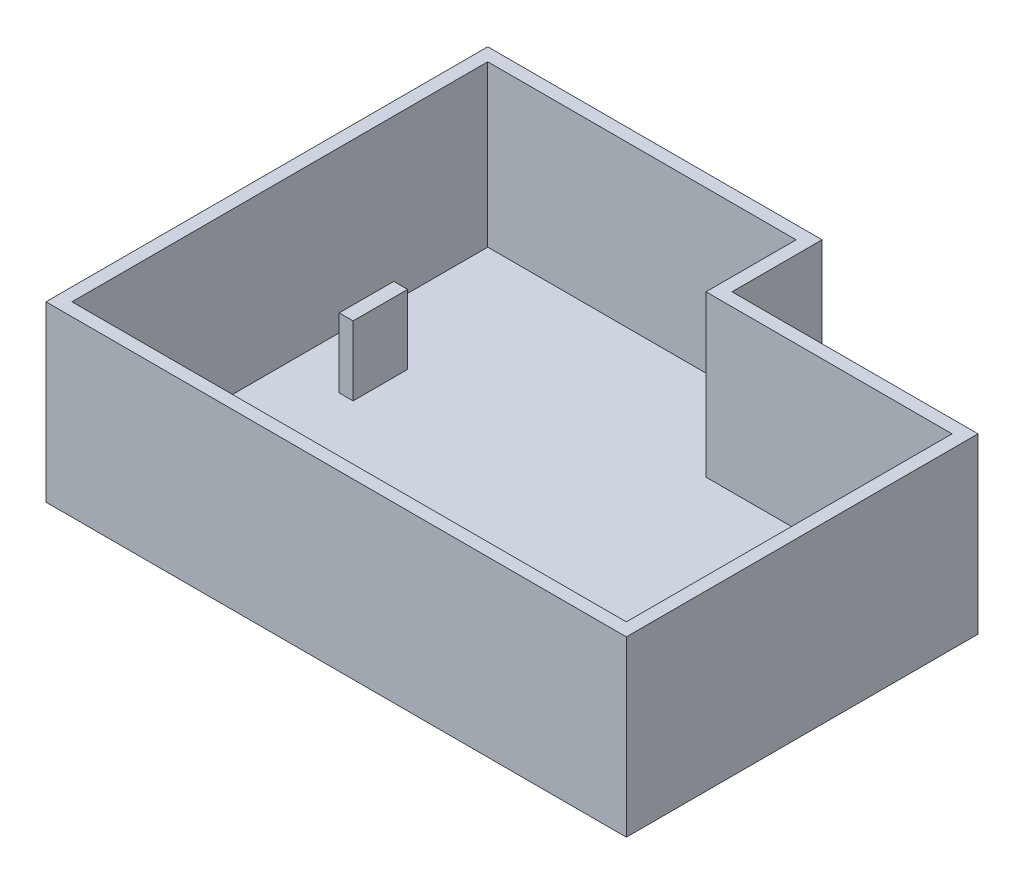
SolidWorks part; units mm, degrees
material "Cedro"
ref_plane "Alzado" through (0, 0, 0) normal (0, 0, 1) x (1, 0, 0)
ref_plane "Planta" through (0, 0, 0) normal (0, 1, 0) x (1, 0, 0)
ref_plane "Vista lateral" through (0, 0, 0) normal (1, 0, 0) x (0, 0, -1)
sketch "Croquis1" plane through (0, 0, 0) normal (0, 1, 0) x (1, 0, 0)
  line L0 (-106.3625, -93.6625) -> (-106.3625, 93.6625)
  line L1 (-101.6, -88.9) -> (101.6, -88.9)
  line L2 (-101.6, -88.9) -> (-101.6, 88.9)
  line L3 (-101.6, 88.9) -> (101.6, 88.9)
  line L4 (101.6, -88.9) -> (101.6, 88.9)
  line L5 (-101.6, -88.9) -> (101.6, 88.9) construction
  line L6 (-101.6, 88.9) -> (101.6, -88.9) construction
  line L7 (-106.3625, 93.6625) -> (106.3625, 93.6625)
  line L8 (106.3625, -93.6625) -> (106.3625, 93.6625)
  line L9 (-106.3625, -93.6625) -> (106.3625, -93.6625)
  point P0 (0, 0)
  dimension "D1" = 203.2
  dimension "D2" = 177.8
  dimension "D3" = 4.7625
extrude "Saliente-Extruir1" add sketch "Croquis1" along normal blind 63.608 contours L1 L4 L3 L2 | L0 L9 L8 L7 L4 L1 L2 L3 region at (-103.528, 0, 0) region at (0, 0, 0)
shell "Vaciado1" thickness 4.7625 removed face at (0, 63.608, 0)
sketch "Croquis2" plane through (0, 4.7625, 0) normal (0, 1, 0) x (1, 0, 0)
  line L0 (-77.47, 10) -> (-77.47, -10)
  line L1 (-101.6, 88.9) -> (101.6, 88.9) construction
  line L3 (10, -64.77) -> (-10, -64.77)
  line L4 (-54.45, 58.42) -> (-34.45, 58.42)
  line L5 (-101.6, -88.9) -> (-101.6, 88.9) construction
  line L6 (-101.6, -88.9) -> (101.6, -88.9) construction
  line L7 (101.6, -88.9) -> (101.6, 88.9) construction
  line L8 (-54.45, 58.42) -> (-54.45, 68.58)
  line L9 (-54.45, 63.5) -> (-34.45, 63.5)
  line L10 (-54.45, 68.58) -> (-34.45, 68.58)
  line L13 (-34.45, 58.42) -> (-34.45, 68.58)
  line L14 (77.47, -18.575) -> (77.47, -38.575)
  line L15 (-54.45, 58.42) -> (-34.45, 68.58) construction
  line L16 (-54.45, 68.58) -> (-34.45, 58.42) construction
  line L17 (72.39, -38.575) -> (82.55, -38.575)
  line L18 (72.39, -38.575) -> (72.39, -18.575)
  line L19 (72.39, -18.575) -> (82.55, -18.575)
  line L20 (82.55, -38.575) -> (82.55, -18.575)
  line L21 (72.39, -38.575) -> (82.55, -18.575) construction
  line L22 (72.39, -18.575) -> (82.55, -38.575) construction
  line L23 (-10, -69.85) -> (10, -69.85)
  line L24 (-10, -69.85) -> (-10, -59.69)
  line L25 (-10, -59.69) -> (10, -59.69)
  line L26 (10, -69.85) -> (10, -59.69)
  line L27 (-10, -69.85) -> (10, -59.69) construction
  line L28 (-10, -59.69) -> (10, -69.85) construction
  line L29 (-72.39, -10) -> (-82.55, -10)
  line L30 (-72.39, -10) -> (-72.39, 10)
  line L31 (-72.39, 10) -> (-82.55, 10)
  line L32 (-82.55, -10) -> (-82.55, 10)
  line L33 (-72.39, -10) -> (-82.55, 10) construction
  line L34 (-72.39, 10) -> (-82.55, -10) construction
  point P1 (-44.45, 63.5)
  point P17 (77.47, -28.575)
  point P23 (0, -64.77)
  point P29 (-77.47, 0)
  dimension "D1" = 24.13
  dimension "D2" = 24.13
  dimension "D3" = 24.13
  dimension "D4" = 25.4
  dimension "D7" = 20
  dimension "D8" = 10.16
extrude "Saliente-Extruir3" add sketch "Croquis2" along normal blind 25.4 contours L9 L13 L10 L8 | L32 L29 L0 L31 | L23 L26 L3 L24 | L17 L20 L19 L14 region at (-80.01, 4.7625, 0) region at (0, 4.7625, 67.31) region at (-44.45, 4.7625, -66.04) region at (80.01, 4.7625, 28.575)
extrude "Saliente-Extruir4" add sketch "Croquis2<5>" along normal blind 6.5 contours L30 L31 L0 L29 | L3 L26 L25 L24 | L19 L18 L17 L14 region at (-74.93, 4.7625, 0) region at (0, 4.7625, 62.23) region at (74.93, 4.7625, 28.575)
sketch "Croquis2<5>" plane through (0, 4.7625, 0) normal (0, 1, 0) x (1, 0, 0) same geometry as "Croquis2"
sketch "Croquis3" plane through (0, 63.608, 0) normal (0, 1, 0) x (1, 0, 0)
  line L0 (11.43, 30.48) -> (106.3625, 30.48)
  line L2 (106.3625, -93.6625) -> (106.3625, 93.6625) construction
  line L3 (11.43, 93.6625) -> (11.43, 30.48)
  line L4 (-106.3625, 93.6625) -> (106.3625, 93.6625) construction
  line L5 (11.43, 93.6625) -> (106.3625, 93.6625)
  line L6 (106.3625, 93.6625) -> (106.3625, 30.48)
  line L7 (-77.47, 10) -> (-77.47, -10) construction
  line L8 (10, -64.77) -> (-10, -64.77) construction
  dimension "D1" = 88.9
  dimension "D2" = 95.25
extrude "Cortar-Extruir1" cut sketch "Croquis3" against normal through all
sketch "Croquis4" plane through (0, 0, 0) normal (0, 1, 0) x (1, 0, 0)
  line L0 (11.43, 93.6625) -> (16.1925, 93.6625)
  line L1 (16.1925, 93.6625) -> (16.1925, 35.2425)
  line L2 (16.1925, 35.2425) -> (106.3625, 35.2425)
  line L3 (106.3625, 35.2425) -> (106.3625, 30.48)
  line L4 (106.3625, 30.48) -> (11.43, 30.48)
  line L5 (11.43, 30.48) -> (11.43, 93.6625)
  dimension "D1" = 4.7625
extrude "Saliente-Extruir5" add sketch "Croquis4" along normal up to surface (63.608 mm away) up to face at (2.286, 63.608, -6.096)
sketch "Croquis5" plane through (0, 0, 0) normal (0, 1, 0) x (1, 0, 0)
  line L0 (16.1925, 35.2425) -> (16.1925, 93.6625) construction
  line L1 (-106.3625, 93.6625) -> (16.1925, 93.6625)
  line L2 (-106.3625, 93.6625) -> (-106.3625, 63.5)
  line L3 (-106.3625, 63.5) -> (16.1925, 63.5)
  line L4 (16.1925, 93.6625) -> (16.1925, 63.5)
  line L5 (-54.45, 63.5) -> (-34.45, 63.5) construction
extrude "Cortar-Extruir2" cut sketch "Croquis5" along normal through all
sketch "Croquis6" plane through (0, 0, 0) normal (0, 1, 0) x (1, 0, 0)
  line L0 (16.1925, 35.2425) -> (16.1925, 63.5) construction
  line L1 (-106.3625, 63.5) -> (16.1925, 63.5)
  line L2 (-106.3625, 63.5) -> (-106.3625, 68.2625)
  line L3 (-106.3625, 68.2625) -> (16.1925, 68.2625)
  line L4 (16.1925, 63.5) -> (16.1925, 68.2625)
  dimension "D1" = 4.7625
extrude "Saliente-Extruir6" add sketch "Croquis6" along normal up to surface (63.608 mm away) up to face at (4.6038, 63.608, -1.6933)
sketch "Croquis7" plane through (0, 63.608, 0) normal (0, 1, 0) x (1, 0, 0)
  line L0 (-77.47, 10) -> (-77.47, -10) construction
  line L1 (-77.47, 17.8902) -> (77.47, 17.8902)
  line L2 (-77.47, 17.8902) -> (-77.47, -64.77)
  line L3 (-77.47, -64.77) -> (77.47, -64.77)
  line L4 (77.47, 17.8902) -> (77.47, -64.77)
  line L5 (77.47, -18.575) -> (77.47, -38.575) construction
  line L6 (10, -64.77) -> (-10, -64.77) construction
extrude "Cortar-Extruir3" cut sketch "Croquis7" against normal up to surface (58.8455 mm away) up to face at (77.47, 4.7625, 28.575)
